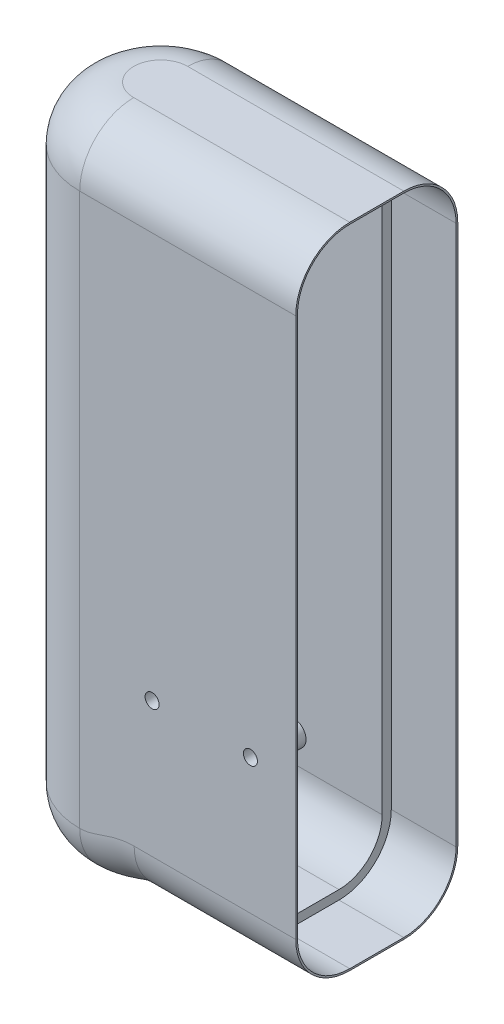
SolidWorks part; units mm, degrees
ref_plane "Front Plane" through (0, 0, 0) normal (0, 0, 1) x (1, 0, 0)
ref_plane "Top Plane" through (0, 0, 0) normal (0, 1, 0) x (1, 0, 0)
ref_plane "Right Plane" through (0, 0, 0) normal (1, 0, 0) x (0, 0, -1)
sketch "Sketch1" plane through (0, 0, 0) normal (0, 1, 0) x (1, 0, 0)
  line L0 (0, 19.05) -> (50.8, 19.05)
  line L1 (50.8, 19.05) -> (50.8, -19.05)
  line L2 (50.8, -19.05) -> (0, -19.05)
  arc A0 (0, 19.05) -> (0, -19.05) centre (0, 0) ccw
  dimension "D1" = 38.1
  dimension "D2" = 50.8
extrude "Boss-Extrude1" add sketch "Sketch1" along normal mid plane 152.4
sketch "Sketch2" plane through (0, -76.2, 0) normal (0, -1, 0) x (1, 0, 0)
  circle A0 centre (0, 0) radius 14.2875
  dimension "D1" = 28.575
extrude "Cut-Extrude1" cut sketch "Sketch2" against normal blind 114.3
fillet "Fillet1" radius 12.7 5 edges at (25.4, 76.2, -19.05) (25.4, 76.2, 19.05) (25.4, -76.2, -19.05) (25.4, -76.2, 19.05) (-19.05, 76.2, 0)
sketch "Sketch3" plane through (50.8, 0, 0) normal (1, 0, 0) x (0, 0, -1)
  line L8 (16.51, -63.5) -> (16.51, 63.5)
  line L9 (6.35, 73.66) -> (-6.35, 73.66)
  line L10 (-16.51, 63.5) -> (-16.51, -63.5)
  line L11 (-6.35, -73.66) -> (6.35, -73.66)
  line L12 (16.51, -63.5) -> (16.51, 63.5)
  line L13 (6.35, 73.66) -> (-6.35, 73.66)
  line L14 (-16.51, 63.5) -> (-16.51, -63.5)
  line L15 (-6.35, -73.66) -> (6.35, -73.66)
  arc A8 (16.51, 63.5) -> (6.35, 73.66) centre (6.35, 63.5) ccw
  arc A9 (-6.35, 73.66) -> (-16.51, 63.5) centre (-6.35, 63.5) ccw
  arc A10 (-16.51, -63.5) -> (-6.35, -73.66) centre (-6.35, -63.5) ccw
  arc A11 (6.35, -73.66) -> (16.51, -63.5) centre (6.35, -63.5) ccw
  arc A12 (16.51, 63.5) -> (6.35, 73.66) centre (6.35, 63.5) ccw
  arc A13 (-6.35, 73.66) -> (-16.51, 63.5) centre (-6.35, 63.5) ccw
  arc A14 (-16.51, -63.5) -> (-6.35, -73.66) centre (-6.35, -63.5) ccw
  arc A15 (6.35, -73.66) -> (16.51, -63.5) centre (6.35, -63.5) ccw
  dimension "D1" = 2.54
extrude "Cut-Extrude2" cut sketch "Sketch3" against normal blind 44.45
sketch "Sketch4" plane through (0, 38.1, 0) normal (0, -1, 0) x (1, 0, 0)
  line L1 (3.81, 11.1125) -> (6.35, 11.1125)
  line L2 (3.81, -11.1125) -> (3.81, 11.1125)
  line L5 (6.35, -12.7988) -> (6.35, 12.7988) construction
  line L6 (3.81, -11.1125) -> (6.35, -11.1125)
  line L7 (6.35, -11.1125) -> (6.35, 11.1125)
  arc A2 (3.81, 11.1125) -> (3.81, -11.1125) centre (0, 0) ccw
  arc A3 (3.81, 11.1125) -> (3.81, -11.1125) centre (0, 0) ccw
  dimension "D1" = 2.54
extrude "Cut-Extrude3" cut sketch "Sketch4" against normal blind 31.75
sketch "Sketch6" plane through (50.8, 0, 0) normal (1, 0, 0) x (0, 0, -1)
  line L0 (-18.65, 63.5) -> (-18.65, -63.5)
  line L1 (-6.35, -75.8) -> (6.35, -75.8)
  line L2 (18.65, -63.5) -> (18.65, 63.5)
  line L3 (6.35, 75.8) -> (-6.35, 75.8)
  line L4 (19.05, -63.5) -> (19.05, 63.5)
  line L5 (6.35, 76.2) -> (-6.35, 76.2)
  line L6 (-19.05, 63.5) -> (-19.05, -63.5)
  line L7 (-6.35, -76.2) -> (6.35, -76.2)
  line L8 (19.05, -63.5) -> (19.05, 63.5) construction
  line L9 (6.35, 76.2) -> (-6.35, 76.2) construction
  line L10 (-19.05, 63.5) -> (-19.05, -63.5) construction
  line L11 (-6.35, -76.2) -> (6.35, -76.2) construction
  arc A0 (-6.35, 75.8) -> (-18.65, 63.5) centre (-6.35, 63.5) ccw
  arc A1 (-18.65, -63.5) -> (-6.35, -75.8) centre (-6.35, -63.5) ccw
  arc A2 (6.35, -75.8) -> (18.65, -63.5) centre (6.35, -63.5) ccw
  arc A3 (18.65, 63.5) -> (6.35, 75.8) centre (6.35, 63.5) ccw
  arc A4 (19.05, 63.5) -> (6.35, 76.2) centre (6.35, 63.5) ccw
  arc A5 (-6.35, 76.2) -> (-19.05, 63.5) centre (-6.35, 63.5) ccw
  arc A6 (-19.05, -63.5) -> (-6.35, -76.2) centre (-6.35, -63.5) ccw
  arc A7 (6.35, -76.2) -> (19.05, -63.5) centre (6.35, -63.5) ccw
  arc A8 (19.05, 63.5) -> (6.35, 76.2) centre (6.35, 63.5) ccw construction
  arc A9 (-6.35, 76.2) -> (-19.05, 63.5) centre (-6.35, 63.5) ccw construction
  arc A10 (-19.05, -63.5) -> (-6.35, -76.2) centre (-6.35, -63.5) ccw construction
  arc A11 (6.35, -76.2) -> (19.05, -63.5) centre (6.35, -63.5) ccw construction
  dimension "D1" = 0
  dimension "D2" = 0.4
extrude "Cut-Extrude4" cut sketch "Sketch6" against normal blind 15.24
sketch "Sketch7" plane through (0, -76.2, 0) normal (0, -1, 0) x (1, 0, 0)
  circle A0 centre (18.415, 0) radius 2.25 construction
  circle A1 centre (18.415, 0) radius 2.25
extrude "Cut-Extrude5" cut sketch "Sketch7" against normal up to next
sketch "Sketch8" plane through (0, 0, 16.51) normal (0, 0, -1) x (-1, 0, 0)
  line L0 (-6.35, 63.5) -> (-6.35, -63.5) construction
  line L2 (-6.35, 63.5) -> (-6.35, -63.5) construction
  line L3 (-50.8, 63.5) -> (-50.8, -63.5) construction
  line L4 (-6.35, -31.75) -> (-50.8, -31.75) construction
  line L5 (-50.8, -76.2) -> (-12.7988, -76.2) construction
  line L6 (-28.575, -31.75) -> (-28.575, 49968.25) construction
  line L7 (-50.8, 63.5) -> (-50.8, -63.5) construction
  circle A0 centre (-17.018, -31.75) radius 1.651
  circle A1 centre (-40.132, -31.75) radius 1.651
  point P14 (-28.575, -31.75)
  point P15 (0, 0)
  point P16 (0, 0)
  dimension "D3" = 3.302
  dimension "D1" = 44.45
  dimension "D2" = 23.114
extrude "Cut-Extrude6" cut sketch "Sketch8" against normal through all
sketch "Sketch9" plane through (0, 0, 19.05) normal (0, 0, 1) x (1, 0, 0)
  circle A0 centre (40.132, -31.75) radius 1.651 construction
  circle A1 centre (17.018, -31.75) radius 1.651 construction
  circle A2 centre (40.132, -31.75) radius 1.651
  circle A3 centre (17.018, -31.75) radius 1.651
extrude "Extrude-Thin1" add sketch "Sketch9" against normal blind 10.16 thin thin type one direction wall 1.27
sketch "Sketch10" plane through (0, 0, 8.89) normal (0, 0, -1) x (-1, 0, 0)
  line L1 (-40.132, -28.829) -> (-17.018, -28.829)
  line L2 (-40.132, -28.829) -> (-40.132, -34.671)
  line L3 (-40.132, -34.671) -> (-17.018, -34.671)
  line L4 (-17.018, -28.829) -> (-17.018, -34.671)
  circle A0 centre (-40.132, -31.75) radius 2.921 construction
  circle A1 centre (-17.018, -31.75) radius 2.921 construction
  point P8 (-39.6794, -29.769)
extrude "Cut-Extrude7" cut sketch "Sketch10" against normal blind 2.54
